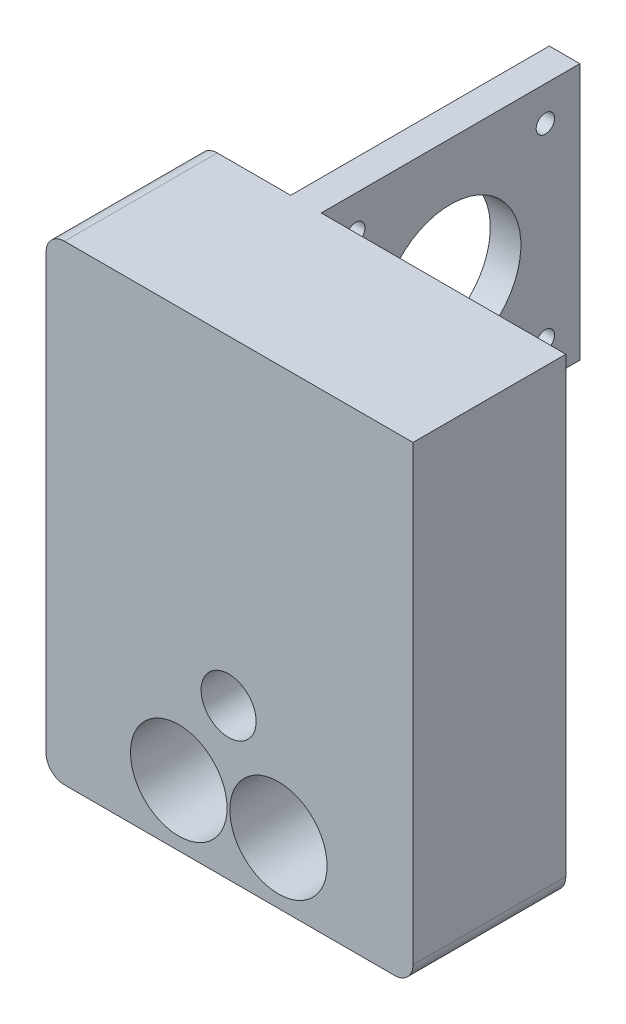
SolidWorks part; units mm, degrees
ref_plane "Plan de face" through (0, 0, 0) normal (0, 0, 1) x (1, 0, 0)
ref_plane "Plan de dessus" through (0, 0, 0) normal (0, 1, 0) x (1, 0, 0)
ref_plane "Plan de droite" through (0, 0, 0) normal (1, 0, 0) x (0, 0, -1)
sketch "Esquisse1" plane through (0, 0, 0) normal (0, 0, 1) x (1, 0, 0)
  line L1 (0, 0) -> (100, 0)
  line L2 (0, 0) -> (0, 100)
  line L3 (0, 100) -> (100, 100)
  line L4 (100, 0) -> (100, 100)
  dimension "D1" = 100
  dimension "D2" = 100
extrude "Boss.-Extru.1" add sketch "Esquisse1" along normal blind 25
sketch "Esquisse2" plane through (0, 0, 0) normal (0, 0, 1) x (1, 0, 0)
  line L1 (100, 0) -> (100, 100) construction
  line L2 (0, 0) -> (100, 0) construction
  circle A0 centre (61.7, 9.9946) radius 7.9
  circle A1 centre (78, 10) radius 7.95
  circle A2 centre (69.8451, 24.6423) radius 4.5
  dimension "D1" = 9
  dimension "D2" = 15.9
  dimension "D3" = 15.8
  dimension "D7" = 10
  dimension "D4" = 16.3
  dimension "D5" = 16.76
  dimension "D6" = 16.76
  dimension "D8" = 22
extrude "Enlèv. mat.-Extru.1" cut sketch "Esquisse2" along normal through all
sketch "Esquisse3" plane through (0, 0, 0) normal (0, 1, 0) x (1, 0, 0)
  line L1 (100, -25) -> (100, 0) construction
  line L2 (0, 0) -> (100, 0) construction
  circle A0 centre (48, -12.5) radius 4.3
  circle A1 centre (92, -12.5) radius 4.3
  dimension "D1" = 8.6
  dimension "D2" = 8.6
  dimension "D4" = 8
  dimension "D6" = 12.5
  dimension "D3" = 44
  dimension "D5" = 12.5
extrude "Enlèv. mat.-Extru.3" cut sketch "Esquisse3" along normal blind 10
sketch "Esquisse4" plane through (0, 0, 0) normal (0, 0, 1) x (1, 0, 0)
  line L0 (100, 0) -> (100, 100) construction
  line L1 (60, 77) -> (55, 77)
  line L2 (60, 77) -> (60, 35)
  line L3 (60, 35) -> (55, 35)
  line L4 (55, 77) -> (55, 35)
  line L5 (0, 0) -> (100, 0) construction
  point P4 (57.5, 77)
  dimension "D1" = 2.5
  dimension "D2" = 42
  dimension "D3" = 40
  dimension "D4" = 35
extrude "Boss.-Extru.2" add sketch "Esquisse4" against normal blind 42.3
sketch "Esquisse5" plane through (60, 0, 0) normal (1, 0, 0) x (0, 0, -1)
  line L0 (0, 0) -> (0, 100) construction
  line L1 (42.3, 35) -> (0, 35) construction
  line L2 (42.3, 77) -> (0, 77) construction
  line L4 (42.3, 35) -> (42.3, 77) construction
  line L5 (0, 0) -> (0, 100) construction
  circle A0 centre (36.65, 71.35) radius 1.5
  circle A1 centre (36.65, 40.65) radius 1.5
  circle A2 centre (5.65, 40.65) radius 1.5
  circle A3 centre (5.65, 71.35) radius 1.5
  dimension "D1" = 3
  dimension "D2" = 3
  dimension "D3" = 3
  dimension "D4" = 3
  dimension "D5" = 5.65
  dimension "D6" = 5.65
  dimension "D7" = 5.65
  dimension "D8" = 5.65
  dimension "D9" = 5.65
  dimension "D10" = 5.65
  dimension "D11" = 5.65
  dimension "D12" = 5.65
extrude "Enlèv. mat.-Extru.4" cut sketch "Esquisse5" against normal blind 12
sketch "Esquisse6" plane through (0, 0, 0) normal (0, 0, 1) x (1, 0, 0)
  line L0 (0, 0) -> (100, 0) construction
  line L1 (40, 0) -> (0, 0)
  line L2 (40, 0) -> (40, 100)
  line L3 (40, 100) -> (0, 100)
  line L4 (0, 0) -> (0, 100)
  dimension "D1" = 40
extrude "Enlèv. mat.-Extru.6" cut sketch "Esquisse6" along normal through all
sketch "Esquisse7" plane through (0, 0, 0) normal (0, 0, 1) x (1, 0, 0)
  line L0 (40, 0) -> (40, 100) construction
  line L1 (100, 100) -> (40, 100)
  line L2 (100, 100) -> (100, 77.3119)
  line L3 (100, 77.3119) -> (40, 77.3119)
  line L4 (40, 100) -> (40, 77.3119)
sketch "Esquisse8" plane through (0, 0, 0) normal (0, 0, -1) x (-1, 0, 0)
  line L1 (-62.691, 21.8527) -> (-63.8522, 29.4431)
  line L2 (-63.8522, 29.4431) -> (-71.0064, 32.2327)
  line L3 (-71.0064, 32.2327) -> (-76.9993, 27.4318)
  line L4 (-76.9993, 27.4318) -> (-75.838, 19.8414)
  line L5 (-75.838, 19.8414) -> (-68.6839, 17.0518)
  line L6 (-68.6839, 17.0518) -> (-62.691, 21.8527)
  circle A0 centre (-69.8451, 24.6423) radius 6.65 construction
  dimension "D1" = 13.3
extrude "Enlèv. mat.-Extru.8" cut sketch "Esquisse8" against normal blind 7.5
sketch "Esquisse9" plane through (0, 0, 0) normal (0, 0, -1) x (-1, 0, 0)
  line L1 (-100, 77) -> (-40, 77)
  line L2 (-100, 77) -> (-100, 100)
  line L3 (-100, 100) -> (-40, 100)
  line L4 (-40, 77) -> (-40, 100)
extrude "Enlèv. mat.-Extru.9" cut sketch "Esquisse9" against normal through all
fillet "Congé2" radius 3 3 edges at (100, 0, 12.5) (40, 77, 12.5) (40, 0, 12.5)
sketch "Esquisse10" plane through (55, 0, 0) normal (-1, 0, 0) x (0, 0, 1)
  line L0 (-42.3, 77) -> (-42.3, 35) construction
  line L1 (-42.3, 35) -> (0, 35) construction
  circle A0 centre (-21.15, 56.15) radius 11.5
  dimension "D1" = 21.15
  dimension "D2" = 21.15
  dimension "D3" = 23
extrude "Enlèv. mat.-Extru.10" cut sketch "Esquisse10" against normal through all
